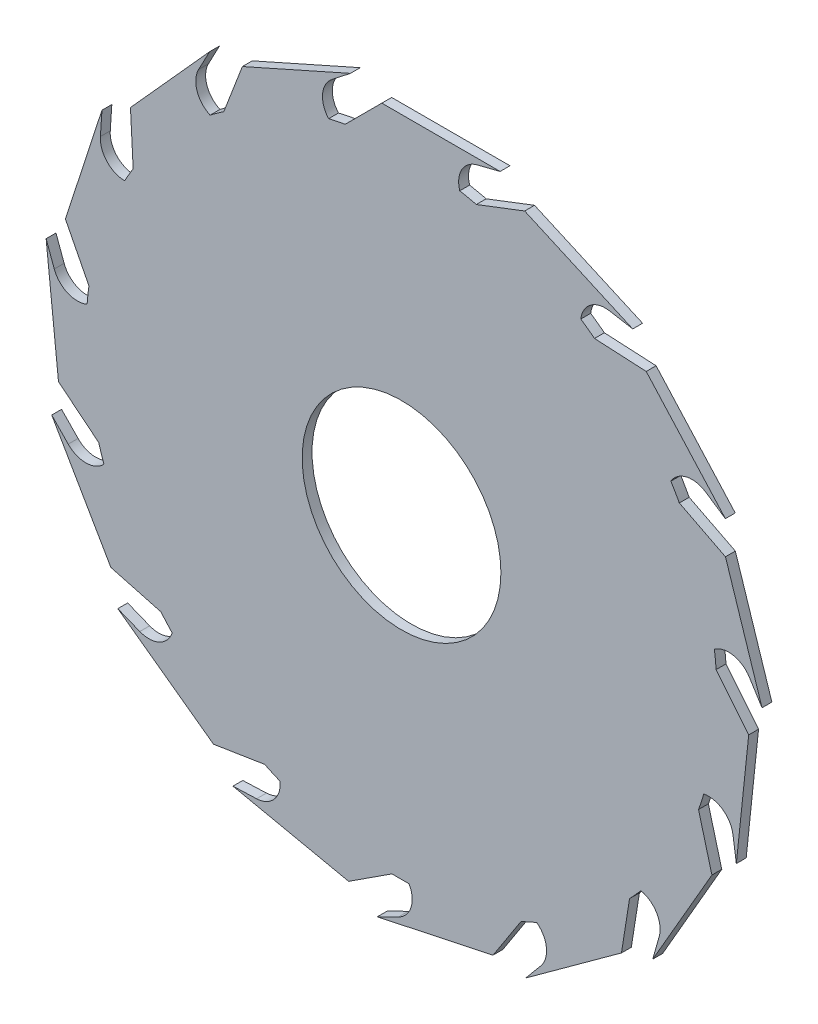
SolidWorks part; units mm, degrees
ref_plane "Front Plane" through (0, 0, 0) normal (0, 0, 1) x (1, 0, 0)
ref_plane "Top Plane" through (0, 0, 0) normal (0, 1, 0) x (1, 0, 0)
ref_plane "Right Plane" through (0, 0, 0) normal (1, 0, 0) x (0, 0, -1)
ref_axis "Axis1" through (63.8149, 0, 0) along (-1, 0, 0)
ref_plane "Plane1" through (0, 0, 0) normal (0, -0.5, -0.866) x (-1, 0, 0)
ref_plane "Plane2" through (0, 11.9062, 20.6222) normal (0, -0.5, -0.866) x (-1, 0, 0)
ref_plane "Plane3" through (0, 12.7, 21.997) normal (0, -0.5, -0.866) x (-1, 0, 0)
sketch "Sketch1" plane through (0, 0, 0) normal (0, 0, 1) x (1, 0, 0)
  circle A0 centre (0, 0) radius 50.8
  dimension "D1" = 101.6
extrude "Boss-Extrude1" add sketch "Sketch1" along normal blind 1.5875 contours A0
sketch "Sketch2" plane through (0, 0, 1.5875) normal (0, 0, 1) x (1, 0, 0)
  circle A0 centre (0, 0) radius 16.002
  dimension "D1" = 32.004
extrude "Cut-Extrude1" cut sketch "Sketch2" against normal up to next
sketch "Sketch4" plane through (0, 0, 1.5875) normal (0, 0, 1) x (1, 0, 0)
  line L0 (-9.525, 49.53) -> (-3.175, 55.88)
  line L1 (-3.175, 55.88) -> (15.875, 55.88)
  line L2 (15.875, 55.88) -> (12.1813, 54.9459)
  line L3 (9.525, 49.53) -> (-9.525, 49.53)
  arc A0 (12.1813, 54.9459) -> (9.525, 49.53) centre (13.1512, 51.1108) ccw
  point P8 (0, 49.53)
  dimension "D1" = 3.81
  dimension "D7" = 1.5808
  dimension "D2" = 19.05
  dimension "D3" = 6.35
  dimension "D4" = 19.05
  dimension "D5" = 55.88
  dimension "D6" = 45
extrude "Boss-Extrude2" add sketch "Sketch4" against normal up to surface (1.5875 mm away) up to face at (16.002, 0, 0)
pattern_circular "CirPattern1" count 15 over 360 about axis through (0, 0, 1.5875) along (0, 0, 1) of "Boss-Extrude2"
